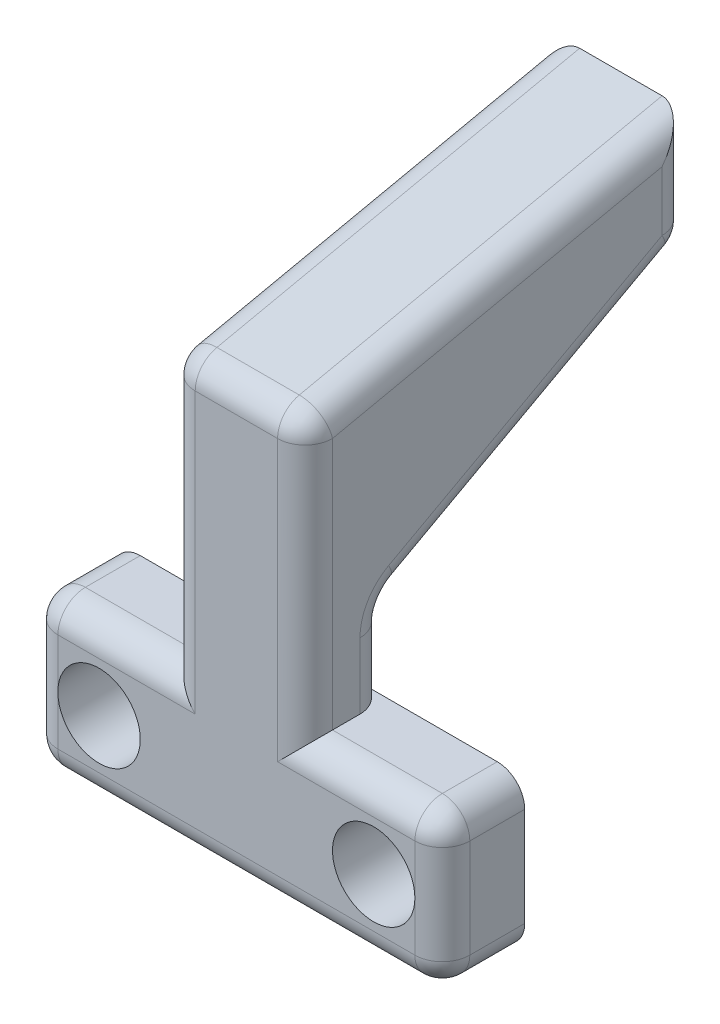
SolidWorks part; units mm, degrees
material "ABS"
ref_plane "Front Plane" through (0, 0, 0) normal (0, 0, 1) x (1, 0, 0)
ref_plane "Top Plane" through (0, 0, 0) normal (0, 1, 0) x (1, 0, 0)
ref_plane "Right Plane" through (0, 0, 0) normal (1, 0, 0) x (0, 0, -1)
sketch "Sketch2" plane through (0, 0, 0) normal (0, 0, 1) x (1, 0, 0)
  line L0 (0, 0) -> (0, 2.8) construction
  line L1 (-7.5, 2.8) -> (7.5, 2.8)
  line L2 (-7.5, 2.8) -> (-7.5, -2.8)
  line L3 (-7.5, -2.8) -> (7.5, -2.8)
  line L4 (7.5, 2.8) -> (7.5, -2.8)
  line L5 (-7.5, 2.8) -> (7.5, -2.8) construction
  line L6 (-7.5, -2.8) -> (7.5, 2.8) construction
  line L8 (-2.5, 2.8) -> (2.5, 2.8)
  line L9 (-2.5, 2.8) -> (-2.5, -2.8)
  line L10 (-2.5, -2.8) -> (2.5, -2.8)
  line L11 (2.5, 2.8) -> (2.5, -2.8)
  line L12 (-2.5, 2.8) -> (2.5, -2.8) construction
  line L13 (-2.5, -2.8) -> (2.5, 2.8) construction
  circle A0 centre (-5, 0) radius 1.5
  circle A1 centre (5, 0) radius 1.5
  point P0 (0, 0)
  dimension "D3" = 3
  dimension "D1" = 15
  dimension "D2" = 5.6
  dimension "D4" = 5
  dimension "D5" = 5
extrude "Boss-Extrude1" add sketch "Sketch2" along normal blind 3 contours L9 L1 L2 L3 A0 | L11 L1 L9 L3 | L1 L11 L3 L4 A1 region at (-5, 2.7249, 0) region at (0, 0, 0) region at (5, 2.7249, 0)
sketch "Sketch5" plane through (0, 0, 3) normal (0, 0, 1) x (1, 0, 0)
  line L0 (-7.5, 2.8) -> (7.5, 2.8) construction
  line L1 (-2.5, 2.8) -> (2.5, 2.8)
  line L2 (-2.5, 2.8) -> (-2.5, 10.8)
  line L3 (-2.5, 10.8) -> (2.5, 10.8)
  line L4 (2.5, 2.8) -> (2.5, 10.8)
  point P6 (0, 10.8)
  dimension "D1" = 5
  dimension "D2" = 8
extrude "Boss-Extrude4" add sketch "Sketch5" against normal up to surface (3 mm away) up to face at (-3.5, 0, 0)
sketch "Sketch6" plane through (2.5, 0, 0) normal (1, 0, 0) x (0, 0, -1)
  line L0 (0, 5.8) -> (11, 11.8)
  line L1 (0, 10.8) -> (0, 2.8) construction
  line L2 (11, 11.8) -> (11, 15.8)
  line L3 (11, 15.8) -> (-3, 12.8)
  line L4 (-3, 12.8) -> (-3, 10.8)
  line L5 (-3, 2.8) -> (-3, 10.8) construction
  line L6 (0, 2.8) -> (-3, 2.8) construction
  line L7 (-3, 10.8) -> (0, 10.8)
  line L8 (0, 10.8) -> (0, 5.8)
  dimension "D1" = 14
  dimension "D2" = 3
  dimension "D3" = 4
  dimension "D4" = 2
  dimension "D5" = 5
extrude "Boss-Extrude5" add sketch "Sketch6" against normal up to surface (5 mm away) up to face at (-2.5, 6.8, 1.5)
fillet "Fillet3" radius 1 22 edges at (2.5, 8.8, -5.5) (0, -2.8, 3) (7.5, 0, 3) (5, 2.8, 3) (-7.5, 0, 3) (-5, 2.8, 3) (2.5, 7.8, 3) (2.5, 14.3, -4) (2.5, 13.8, -11) (2.5, 4.3, 0) (-2.5, 14.3, -4) (-2.5, 13.8, -11) (-2.5, 4.3, 0) (-2.5, 8.8, -5.5) (-2.5, 7.8, 3) (0, 11.8, -11) (0, 5.8, 0) (0, 12.8, 3) (7.5, -2.8, 1.5) (7.5, 2.8, 1.5) (-7.5, -2.8, 1.5) (-7.5, 2.8, 1.5)
